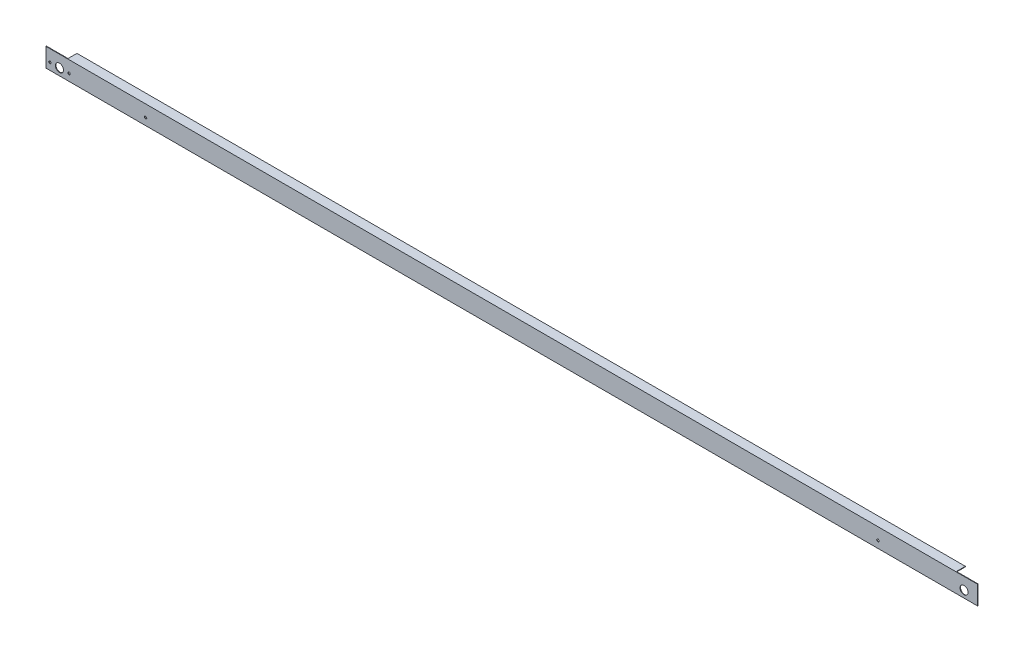
SolidWorks part; units mm, degrees
material "Galvanized Steel"
ref_plane "Front Plane" through (0, 0, 0) normal (0, 0, 1) x (1, 0, 0)
ref_plane "Top Plane" through (0, 0, 0) normal (0, 1, 0) x (1, 0, 0)
ref_plane "Right Plane" through (0, 0, 0) normal (1, 0, 0) x (0, 0, -1)
sketch "Sketch1" plane through (0, 0, 0) normal (1, 0, 0) x (0, 0, -1)
  line L0 (0, 0) -> (0, 63.5)
  line L1 (0, 63.5) -> (44.45, 63.5)
  line L4 (2.3813, 2.3813) -> (2.3813, 61.1187)
  line L5 (2.3813, 61.1187) -> (44.45, 61.1187)
  line L6 (44.45, 63.5) -> (44.45, 61.1187)
  line L8 (0, 0) -> (39.0507, 0) construction
  line L9 (2.3813, 2.3813) -> (39.0507, 2.3813) construction
  line L10 (0, 0) -> (0, -25.4)
  line L14 (2.3813, -25.4) -> (2.3813, 2.3813)
  line L15 (0, -25.4) -> (2.3813, -25.4)
  point P9 (0, 0)
  dimension "D1" = 63.5
  dimension "D2" = 44.45
  dimension "D4" = 25.4
  dimension "D3" = 2.3813
extrude "Boss-Extrude1" add sketch "Sketch1" along normal blind 4394.2
sketch "Sketch2" plane through (0, 0, -2.3813) normal (0, 0, -1) x (-1, 0, 0)
  line L0 (-4394.2, 63.5) -> (0, 63.5) construction
  line L1 (-4394.2, -25.4) -> (-4394.2, 61.1187) construction
  line L2 (0, -25.4) -> (0, 61.1187) construction
  circle A0 centre (-4330.7, 7.62) radius 19.05
  circle A1 centre (-63.5, 7.62) radius 19.05
  circle A2 centre (-18.4547, 7.62) radius 5.5562
  circle A3 centre (-108.5453, 7.62) radius 5.5563
  point P14 (0, 0)
  dimension "D1" = 38.1
  dimension "D4" = 38.1
  dimension "D7" = 11.1125
  dimension "D8" = 11.1125
  dimension "D2" = 55.88
  dimension "D3" = 63.5
  dimension "D5" = 55.88
  dimension "D6" = 63.5
  dimension "D9" = 45.0453
  dimension "D10" = 45.0453
extrude "Cut-Extrude1" cut sketch "Sketch2" against normal up to next
sketch "Sketch3" plane through (0, 0, -2.3813) normal (0, 0, -1) x (-1, 0, 0)
  line L19 (-4394.2, 61.1187) -> (0, 61.1187) construction
  line L20 (-4394.2, 63.5) -> (-4292.6, 63.5)
  line L21 (-4394.2, 63.5) -> (-4394.2, 61.1187)
  line L22 (-4394.2, 61.1187) -> (-4292.6, 61.1187)
  line L23 (-4292.6, 63.5) -> (-4292.6, 61.1187)
  line L25 (0, 63.5) -> (-101.6, 63.5)
  line L26 (0, 63.5) -> (0, 61.1187)
  line L27 (0, 61.1187) -> (-101.6, 61.1187)
  line L28 (-101.6, 63.5) -> (-101.6, 61.1187)
  dimension "D1" = 101.6
  dimension "D2" = 101.6
extrude "Cut-Extrude4" cut sketch "Sketch3" along normal up to next
sketch "Sketch4" plane through (0, 0, -2.3813) normal (0, 0, -1) x (-1, 0, 0)
  circle A12 centre (-3924.3, 7.62) radius 5.588
  circle A13 centre (-4330.7, 7.62) radius 19.05 construction
  circle A14 centre (-4330.7, 7.62) radius 19.05
  circle A15 centre (-469.9, 7.62) radius 5.588
  circle A16 centre (-63.5, 7.62) radius 19.05 construction
  circle A17 centre (-63.5, 7.62) radius 19.05
  point P2 (0, 0)
  dimension "D3" = 406.4
  dimension "D1" = 11.176
  dimension "D2" = 406.4
extrude "Cut-Extrude5" cut sketch "Sketch4" against normal up to next (2.3813 mm away)
